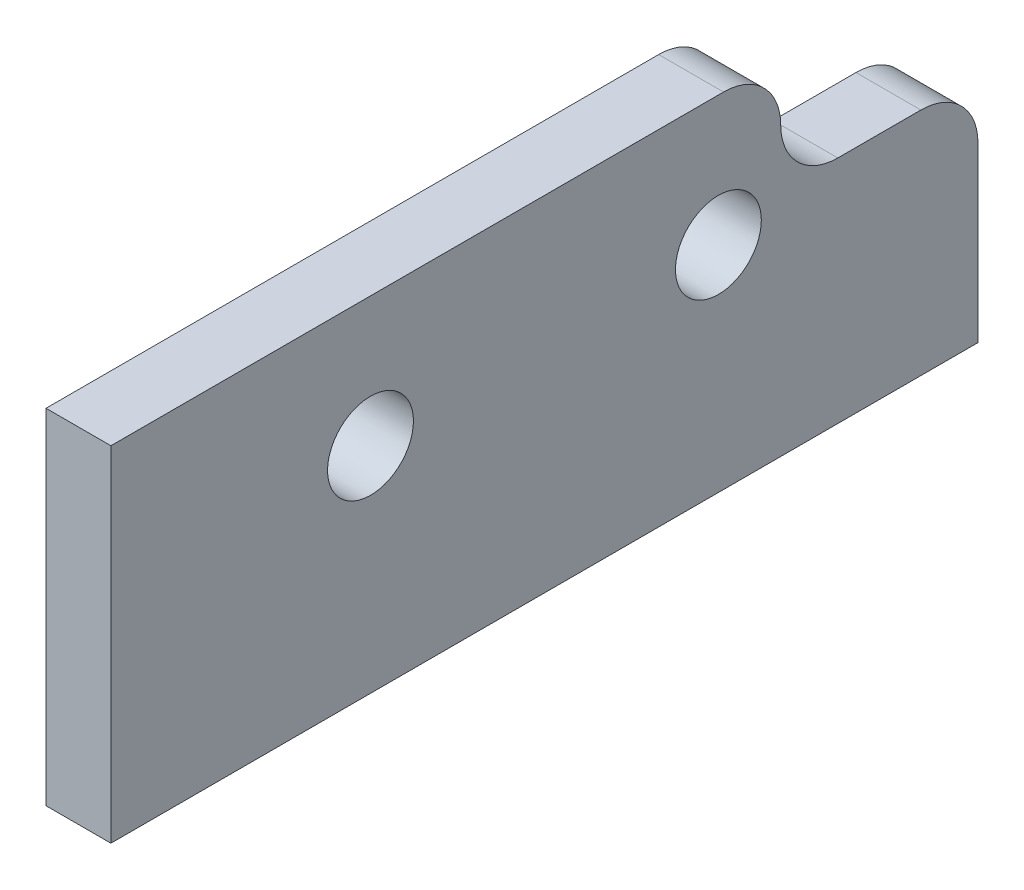
SolidWorks part; units mm, degrees
material "Silicon Rubber"
ref_plane "Front Plane" through (0, 0, 0) normal (0, 0, 1) x (1, 0, 0)
ref_plane "Top Plane" through (0, 0, 0) normal (0, 1, 0) x (1, 0, 0)
ref_plane "Right Plane" through (0, 0, 0) normal (1, 0, 0) x (0, 0, -1)
sketch "Sketch1" plane through (0, 0, 0) normal (1, 0, 0) x (0, 0, -1)
  line L13 (-21.209, -8.4201) -> (21.209, -8.4201)
  line L14 (-21.209, -8.4201) -> (-21.209, 8.4201)
  line L15 (-21.209, 8.4201) -> (21.209, 8.4201)
  line L16 (21.209, -8.4201) -> (21.209, 8.4201)
  line L17 (-21.209, -8.4201) -> (21.209, 8.4201) construction
  line L18 (-21.209, 8.4201) -> (21.209, -8.4201) construction
  point P0 (0, 0)
  dimension "D2" = 42.418
  dimension "D1" = 16.8402
extrude "Boss-Extrude1" add sketch "Sketch1" along normal blind 3.175
sketch "Sketch3" plane through (3.175, 0, 0) normal (1, 0, 0) x (0, 0, -1)
  line L7 (-21.209, 8.4201) -> (-21.209, -4.2799) construction
  line L8 (-21.209, 8.4201) -> (-21.209, -8.4201) construction
  line L9 (-21.209, 2.0701) -> (21.209, 2.0701) construction
  line L10 (21.209, -8.4201) -> (21.209, 8.4201) construction
  circle A2 centre (-8.509, 2.0701) radius 2.1
  circle A3 centre (8.509, 2.0701) radius 2.1
  dimension "D1" = 12.7
  dimension "D4" = 4.2
  dimension "D5" = 12.7
  dimension "D3" = 12.7
extrude "Cut-Extrude1" cut sketch "Sketch3" against normal through all
sketch "Sketch4" plane through (3.175, 0, 0) normal (1, 0, 0) x (0, 0, -1)
  line L1 (21.209, 8.4201) -> (11.557, 8.4201)
  line L2 (21.209, 8.4201) -> (21.209, 2.8321)
  line L3 (21.209, 2.8321) -> (11.557, 2.8321)
  line L4 (11.557, 8.4201) -> (11.557, 2.8321)
  dimension "D1" = 5.588
  dimension "D2" = 9.652
extrude "Cut-Extrude2" cut sketch "Sketch4" against normal through all
fillet "Fillet1" radius 2.794 3 edges at (1.5875, 2.8321, -21.209) (1.5875, 8.4201, -11.557) (1.5875, 2.8321, -11.557)
